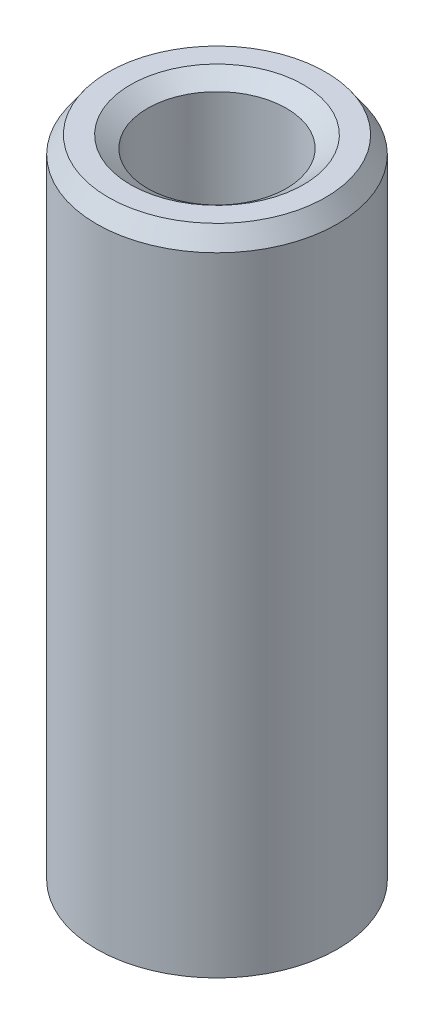
SolidWorks part; units mm, degrees
ref_plane "Front Plane" through (0, 0, 0) normal (0, 0, 1) x (1, 0, 0)
ref_plane "Top Plane" through (0, 0, 0) normal (0, 1, 0) x (1, 0, 0)
ref_plane "Right Plane" through (0, 0, 0) normal (1, 0, 0) x (0, 0, -1)
sketch "Sketch1" plane through (0, 0, 0) normal (0, 1, 0) x (1, 0, 0)
  circle A0 centre (0, 0) radius 22.5
  dimension "SLEEVE_OD" = 45
extrude "Boss-Extrude1" add sketch "Sketch1" along normal blind 122.7126
sketch "Sketch2" plane through (0, 0, 0) normal (0, 1, 0) x (1, 0, 0)
  circle A0 centre (0, 0) radius 12.9701
  dimension "BORE_D" = 25.9403
extrude "Cut-Extrude1" cut sketch "Sketch2" along normal through all
chamfer "Chamfer1" distance 3.1975 angle 34.633 4 edges at (0, 122.7126, 12.9701) (0, 0, 12.9701) (0, 0, 22.5) (0, 122.7126, 22.5) first distance on face at (0, 122.7126, 12.9701) first distance on face at (0, 0, 12.9701) first distance on face at (0, 122.7126, 22.5)
